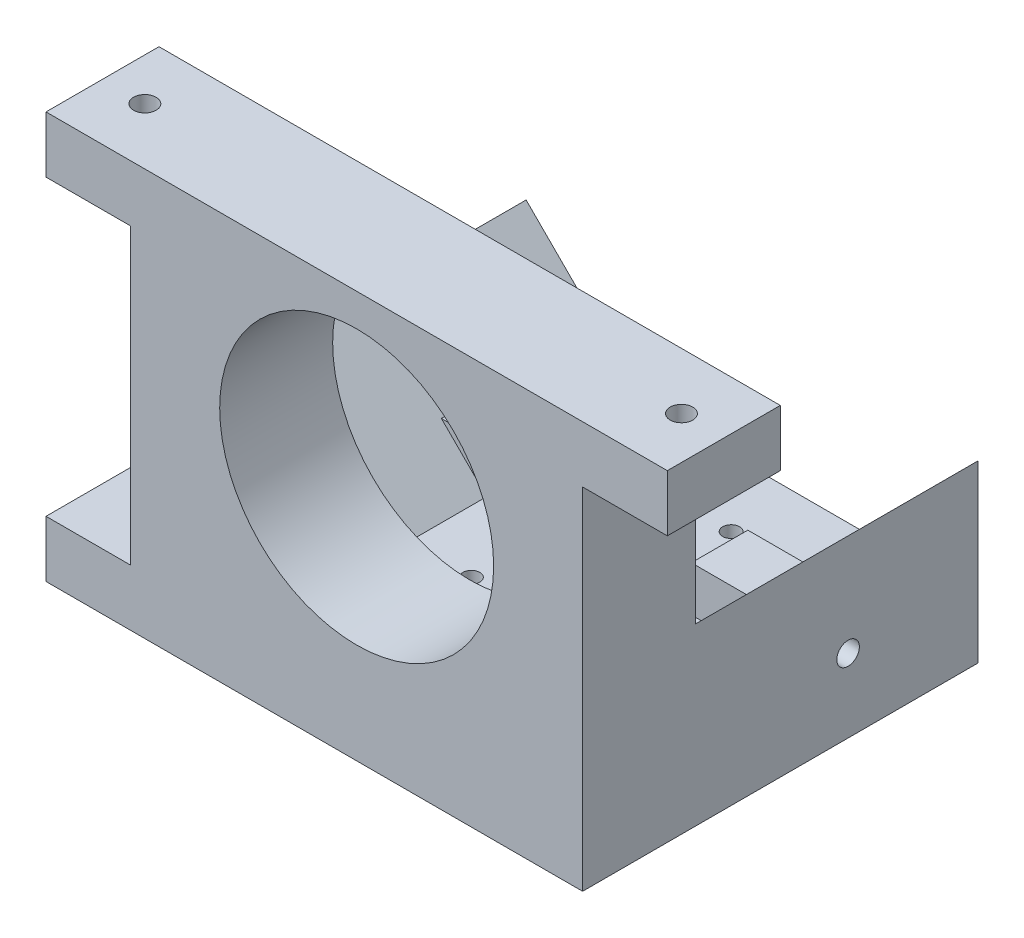
SolidWorks part; units mm, degrees
ref_plane "Front Plane" through (0, 0, 0) normal (0, 0, 1) x (1, 0, 0)
ref_plane "Top Plane" through (0, 0, 0) normal (0, 1, 0) x (1, 0, 0)
ref_plane "Right Plane" through (0, 0, 0) normal (1, 0, 0) x (0, 0, -1)
sketch "Sketch1" plane through (0, 0, 0) normal (0, 0, 1) x (1, 0, 0)
  line L1 (-40, -30) -> (40, -30)
  line L2 (-40, -30) -> (-40, 30)
  line L3 (-40, 30) -> (40, 30)
  line L4 (40, -30) -> (40, 30)
  line L5 (-40, -30) -> (40, 30) construction
  line L6 (-40, 30) -> (40, -30) construction
  circle A0 centre (0, 0) radius 24.25
  dimension "D1" = 48.5
  dimension "D2" = 80
  dimension "D3" = 60
extrude "Boss-Extrude1" add sketch "Sketch1" along normal blind 20
sketch "Sketch4" plane through (40, 0, 0) normal (1, 0, 0) x (0, 0, -1)
  line L0 (0, -30) -> (0, 30) construction
  line L1 (-20, 30) -> (0, 30)
  line L2 (-20, 30) -> (-20, 20)
  line L3 (-20, 20) -> (0, 20)
  line L4 (0, 30) -> (0, 20)
  line L5 (-20, 30) -> (0, 20) construction
  line L6 (-20, 20) -> (0, 30) construction
  point P4 (-10, 25)
  dimension "D1" = 10
extrude "Boss-Extrude3" add sketch "Sketch4" along normal blind 15
sketch "Sketch5" plane through (0, 30, 0) normal (0, 1, 0) x (1, 0, 0)
  line L0 (55, -10) -> (-40, -10) construction
  line L1 (55, 0) -> (55, -20) construction
  line L2 (-40, -20) -> (-40, 0) construction
  line L3 (40, 0) -> (40, -20) construction
  line L4 (55, 0) -> (-40, 0) construction
  line L5 (55, -20) -> (-40, -20) construction
  circle A0 centre (47.5, -10) radius 2
  dimension "D1" = 4
  dimension "D2" = 7.5
extrude "Cut-Extrude2" cut sketch "Sketch5" against normal up to surface (10 mm away) up to face at (47.5, 20, 10)
sketch "Sketch6" plane through (0, -30, 0) normal (0, -1, 0) x (-1, 0, 0)
  line L1 (40, -20) -> (-40, -20)
  line L2 (40, -20) -> (40, 0)
  line L3 (40, 0) -> (-40, 0)
  line L4 (-40, -20) -> (-40, 0)
  line L5 (40, -20) -> (-40, 0) construction
  line L6 (40, 0) -> (-40, -20) construction
  point P4 (0, -10)
extrude "Boss-Extrude4" add sketch "Sketch6" along normal blind 2
sketch "Sketch8" plane through (0, 0, 0) normal (0, 0, -1) x (-1, 0, 0)
  line L0 (-40, -11) -> (-19, -32)
  line L1 (-40, -32) -> (-40, 20) construction
  line L2 (40, -32) -> (-40, -32) construction
  line L3 (-19, -32) -> (-40, -32)
  line L4 (-40, -32) -> (-40, -11)
  dimension "D1" = 21
extrude "Boss-Extrude6" add sketch "Sketch8" along normal blind 50
sketch "Sketch9" plane through (40, 0, 0) normal (1, 0, 0) x (0, 0, -1)
  line L0 (-20, -32) -> (-20, 20) construction
  line L1 (50, -32) -> (-20, -32) construction
  circle A0 centre (27, -29) radius 2
  dimension "D1" = 4
  dimension "D2" = 47
  dimension "D3" = 3
extrude "Cut-Extrude3" cut sketch "Sketch9" against normal through all
ref_plane "Plane1" through (19, 0, 0) normal (-1, 0, 0) x (0, 0, 1)
sketch "Sketch10" plane through (19, 0, 0) normal (-1, 0, 0) x (0, 0, 1)
  line L0 (-50, -32) -> (0, -32) construction
  line L1 (-32, -32) -> (-22, -32)
  line L2 (-32, -32) -> (-32, -24)
  line L3 (-32, -24) -> (-22, -24)
  line L4 (-22, -32) -> (-22, -24)
  line L5 (-32, -32) -> (-22, -24) construction
  line L6 (-32, -24) -> (-22, -32) construction
  circle A2 centre (-27, -29) radius 2 construction
  point P4 (-27, -28)
  dimension "D1" = 8
  dimension "D2" = 10
extrude "Boss-Extrude7" add sketch "Sketch10" along normal blind 1.75 and the other way up to surface other way up to face at (24, -27, -27)
sketch "Sketch11" plane through (17.25, 0, 0) normal (-1, 0, 0) x (0, 0, 1)
  circle A0 centre (-27, -29) radius 2
  circle A1 centre (-27, -29) radius 2 construction
extrude "Cut-Extrude4" cut sketch "Sketch11" against normal up to surface (22.75 mm away) up to face at (40, -29, -29)
fillet "Fillet1" radius 0.001 2 edges at (17.25, -28, -22) (17.25, -28, -32)
sketch "Sketch12" plane through (0, -32, 0) normal (0, -1, 0) x (1, 0, 0)
  line L0 (0, 20) -> (0, -50) construction
  line L1 (-40, 20) -> (40, 20)
  line L2 (-40, 20) -> (-40, -50)
  line L3 (-40, -50) -> (40, -50)
  line L4 (40, 20) -> (40, -50)
  line L5 (-40, 20) -> (40, -50) construction
  line L6 (-40, -50) -> (40, 20) construction
  line L7 (-8, -8.3) -> (8, -8.3) construction
  line L8 (-8, -8.3) -> (-8, -38.3) construction
  line L9 (-8, -38.3) -> (8, -38.3) construction
  line L10 (8, -38.3) -> (8, -8.3) construction
  line L11 (-40, 0) -> (19, 0) construction
  circle A0 centre (-8, -8.3) radius 1.5
  circle A1 centre (8, -8.3) radius 1.5
  circle A2 centre (8, -38.3) radius 1.5
  circle A3 centre (-8, -38.3) radius 1.5
  point P4 (0, -15)
  point P11 (0, -8.3)
  dimension "D4" = 3
  dimension "D1" = 16
  dimension "D2" = 30
  dimension "D3" = 8.3
extrude "Boss-Extrude8" add sketch "Sketch12" along normal blind 10
ref_plane "Plane2" through (0, 0, 0) normal (1, 0, 0) x (0, 0, -1)
mirror "Mirror1" about plane through (0, 0, 0) normal (1, 0, 0) of "Fillet1", "Cut-Extrude4", "Boss-Extrude7", "Cut-Extrude3", "Boss-Extrude6", "Boss-Extrude4", "Cut-Extrude2", "Boss-Extrude3"
sketch "Sketch13" plane through (-40, 0, 0) normal (-1, 0, 0) x (0, 0, 1)
  line L0 (20, 20) -> (20, -42) construction
  line L1 (20, -42) -> (0, -42)
  line L2 (20, -42) -> (20, -32)
  line L3 (20, -32) -> (0, -32)
  line L4 (0, -42) -> (0, -32)
  line L5 (20, -42) -> (0, -32) construction
  line L6 (20, -32) -> (0, -42) construction
  line L7 (20, 20) -> (0, 20) construction
  point P4 (10, -37)
  point P9 (0, 0)
  dimension "D1" = 10
  dimension "D2" = 52
extrude "Boss-Extrude9" add sketch "Sketch13" along normal blind 15
